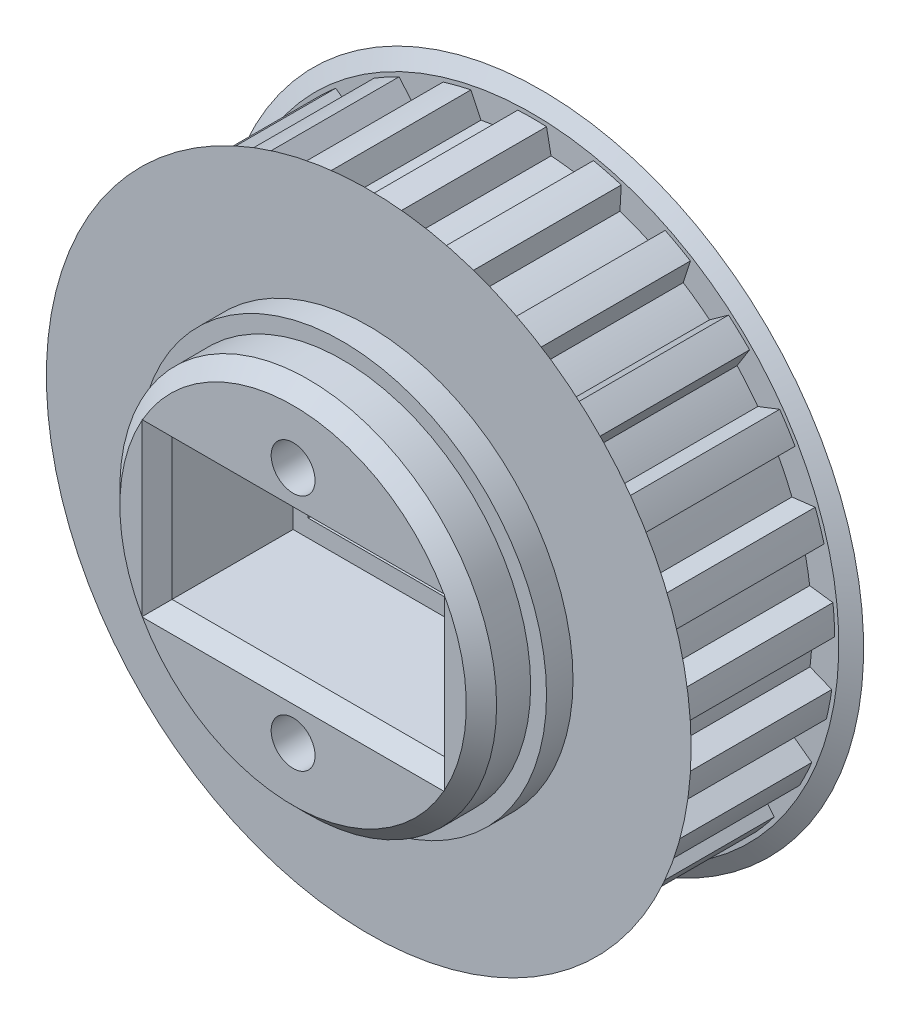
SolidWorks part; units mm, degrees
material "ABS"
ref_plane "Alzado" through (0, 0, 0) normal (0, 0, 1) x (1, 0, 0)
ref_plane "Planta" through (0, 0, 0) normal (0, 1, 0) x (1, 0, 0)
ref_plane "Vista lateral" through (0, 0, 0) normal (1, 0, 0) x (0, 0, -1)
sketch "Croquis1" plane through (0, 0, 0) normal (0, 0, 1) x (1, 0, 0)
  line L0 (0, 0) -> (0, 14.5885) construction
  line L1 (-0.95, 19.9774) -> (-1.25, 18.4577)
  line L2 (0.95, 19.9774) -> (1.25, 18.4577)
  line L3 (5.8883, 19.1135) -> (5.801, 17.567)
  line L4 (4.048, 19.5861) -> (3.3795, 18.1887)
  line L5 (10.4567, 17.0487) -> (9.9875, 15.5724)
  line L6 (8.7917, 17.964) -> (7.7967, 16.7768)
  line L7 (14.368, 13.9126) -> (13.5464, 12.5994)
  line L8 (12.983, 15.2132) -> (11.724, 14.3108)
  line L9 (17.3765, 9.9023) -> (16.2542, 8.8347)
  line L10 (16.3585, 11.5066) -> (14.9146, 10.9456)
  line L11 (19.2932, 5.2699) -> (17.9406, 4.5149)
  line L12 (18.7061, 7.0769) -> (17.1681, 6.8926)
  line L13 (19.9977, 0.3063) -> (18.4998, -0.0886)
  line L14 (19.8784, 2.2025) -> (18.3428, 2.4065)
  line L15 (19.4456, -4.6766) -> (17.8966, -4.6865)
  line L16 (19.8016, -2.8102) -> (18.365, -2.2308)
  line L17 (17.6716, -9.3656) -> (16.1688, -8.9899)
  line L18 (18.4806, -7.6464) -> (17.2333, -6.7279)
  line L19 (14.7873, -13.4661) -> (13.4251, -12.7285)
  line L20 (15.9984, -12.0021) -> (15.0187, -10.8023)
  line L21 (10.9739, -16.7205) -> (9.8379, -15.6673)
  line L22 (12.511, -15.6037) -> (11.8604, -14.1979)
  line L23 (6.4709, -18.9243) -> (5.6325, -17.6217)
  line L24 (8.2375, -18.2248) -> (7.957, -16.7014)
  line L25 (1.5613, -19.939) -> (1.0732, -18.4688)
  line L26 (3.4463, -19.7008) -> (3.5535, -18.1555)
  line L27 (-3.4463, -19.7008) -> (-3.5535, -18.1555)
  line L28 (-1.5613, -19.939) -> (-1.0732, -18.4688)
  line L29 (-8.2375, -18.2248) -> (-7.957, -16.7014)
  line L30 (-6.4709, -18.9243) -> (-5.6325, -17.6217)
  line L31 (-12.511, -15.6037) -> (-11.8604, -14.1979)
  line L32 (-10.9739, -16.7205) -> (-9.8379, -15.6673)
  line L33 (-15.9984, -12.0021) -> (-15.0187, -10.8023)
  line L34 (-14.7873, -13.4661) -> (-13.4251, -12.7285)
  line L35 (-18.4806, -7.6464) -> (-17.2333, -6.7279)
  line L36 (-17.6716, -9.3656) -> (-16.1688, -8.9899)
  line L37 (-19.8016, -2.8102) -> (-18.365, -2.2308)
  line L38 (-19.4456, -4.6766) -> (-17.8966, -4.6865)
  line L39 (-19.8784, 2.2025) -> (-18.3428, 2.4065)
  line L40 (-19.9977, 0.3063) -> (-18.4998, -0.0886)
  line L41 (-18.7061, 7.0769) -> (-17.1681, 6.8926)
  line L42 (-19.2932, 5.2699) -> (-17.9406, 4.5149)
  line L43 (-16.3585, 11.5066) -> (-14.9146, 10.9456)
  line L44 (-17.3765, 9.9023) -> (-16.2542, 8.8347)
  line L45 (-12.983, 15.2132) -> (-11.724, 14.3108)
  line L46 (-14.368, 13.9126) -> (-13.5464, 12.5994)
  line L47 (-8.7917, 17.964) -> (-7.7967, 16.7768)
  line L48 (-10.4567, 17.0487) -> (-9.9875, 15.5724)
  line L49 (-4.048, 19.5861) -> (-3.3795, 18.1887)
  line L50 (-5.8883, 19.1135) -> (-5.801, 17.567)
  arc A1 (3.3795, 18.1887) -> (1.25, 18.4577) centre (0, 0) ccw
  arc A9 (-4.048, 19.5861) -> (-5.8883, 19.1135) centre (0, 0) ccw
  arc A10 (-8.7917, 17.964) -> (-10.4567, 17.0487) centre (0, 0) ccw
  arc A11 (5.8883, 19.1135) -> (4.048, 19.5861) centre (0, 0) ccw
  arc A12 (0.95, 19.9774) -> (-0.95, 19.9774) centre (0, 0) ccw
  arc A16 (10.4567, 17.0487) -> (8.7917, 17.964) centre (0, 0) ccw
  arc A17 (14.368, 13.9126) -> (12.983, 15.2132) centre (0, 0) ccw
  arc A18 (17.3765, 9.9023) -> (16.3585, 11.5066) centre (0, 0) ccw
  arc A19 (19.2932, 5.2699) -> (18.7061, 7.0769) centre (0, 0) ccw
  arc A20 (19.9977, 0.3063) -> (19.8784, 2.2025) centre (0, 0) ccw
  arc A21 (19.4456, -4.6766) -> (19.8016, -2.8102) centre (0, 0) ccw
  arc A22 (17.6716, -9.3656) -> (18.4806, -7.6464) centre (0, 0) ccw
  arc A23 (14.7873, -13.4661) -> (15.9984, -12.0021) centre (0, 0) ccw
  arc A24 (10.9739, -16.7205) -> (12.511, -15.6037) centre (0, 0) ccw
  arc A25 (6.4709, -18.9243) -> (8.2375, -18.2248) centre (0, 0) ccw
  arc A26 (-12.511, -15.6037) -> (-10.9739, -16.7205) centre (0, 0) ccw
  arc A27 (-15.9984, -12.0021) -> (-14.7873, -13.4661) centre (0, 0) ccw
  arc A28 (-18.4806, -7.6464) -> (-17.6716, -9.3656) centre (0, 0) ccw
  arc A29 (-19.8784, 2.2025) -> (-19.9977, 0.3063) centre (0, 0) ccw
  arc A30 (-18.7061, 7.0769) -> (-19.2932, 5.2699) centre (0, 0) ccw
  arc A31 (-16.3585, 11.5066) -> (-17.3765, 9.9023) centre (0, 0) ccw
  arc A32 (-12.983, 15.2132) -> (-14.368, 13.9126) centre (0, 0) ccw
  arc A33 (-8.2375, -18.2248) -> (-6.4709, -18.9243) centre (0, 0) ccw
  arc A34 (-3.4463, -19.7008) -> (-1.5613, -19.939) centre (0, 0) ccw
  arc A35 (1.5613, -19.939) -> (3.4463, -19.7008) centre (0, 0) ccw
  arc A36 (7.7967, 16.7768) -> (5.801, 17.567) centre (0, 0) ccw
  arc A37 (11.724, 14.3108) -> (9.9875, 15.5724) centre (0, 0) ccw
  arc A39 (-1.25, 18.4577) -> (-3.3795, 18.1887) centre (0, 0) ccw
  arc A43 (14.9146, 10.9456) -> (13.5464, 12.5994) centre (0, 0) ccw
  arc A44 (17.1681, 6.8926) -> (16.2542, 8.8347) centre (0, 0) ccw
  arc A45 (18.3428, 2.4065) -> (17.9406, 4.5149) centre (0, 0) ccw
  arc A46 (18.365, -2.2308) -> (18.4998, -0.0886) centre (0, 0) ccw
  arc A47 (17.2333, -6.7279) -> (17.8966, -4.6865) centre (0, 0) ccw
  arc A48 (15.0187, -10.8023) -> (16.1688, -8.9899) centre (0, 0) ccw
  arc A49 (11.8604, -14.1979) -> (13.4251, -12.7285) centre (0, 0) ccw
  arc A50 (7.957, -16.7014) -> (9.8379, -15.6673) centre (0, 0) ccw
  arc A51 (3.5535, -18.1555) -> (5.6325, -17.6217) centre (0, 0) ccw
  arc A52 (-1.0732, -18.4688) -> (1.0732, -18.4688) centre (0, 0) ccw
  arc A53 (-5.6325, -17.6217) -> (-3.5535, -18.1555) centre (0, 0) ccw
  arc A54 (-9.8379, -15.6673) -> (-7.957, -16.7014) centre (0, 0) ccw
  arc A55 (-13.4251, -12.7285) -> (-11.8604, -14.1979) centre (0, 0) ccw
  arc A56 (-16.1688, -8.9899) -> (-15.0187, -10.8023) centre (0, 0) ccw
  arc A57 (-17.8966, -4.6865) -> (-17.2333, -6.7279) centre (0, 0) ccw
  arc A58 (-18.4998, -0.0886) -> (-18.365, -2.2308) centre (0, 0) ccw
  arc A59 (-17.9406, 4.5149) -> (-18.3428, 2.4065) centre (0, 0) ccw
  arc A60 (-16.2542, 8.8347) -> (-17.1681, 6.8926) centre (0, 0) ccw
  arc A61 (-13.5464, 12.5994) -> (-14.9146, 10.9456) centre (0, 0) ccw
  arc A62 (-9.9875, 15.5724) -> (-11.724, 14.3108) centre (0, 0) ccw
  arc A63 (-5.801, 17.567) -> (-7.7967, 16.7768) centre (0, 0) ccw
  arc A71 (-19.8016, -2.8102) -> (-19.4456, -4.6766) centre (0, 0) ccw
  circle A72 centre (0, 0) radius 1.5
  point P10 (-3.2613, 18.1887)
  point P151 (0, 0)
  dimension "D1" = 20
  dimension "D6" = 3
  dimension "D5" = 1.5
  dimension "D2" = 2.5
  dimension "D3" = 1.9
  dimension "D4" = 25
extrude "Saliente-Extruir1" add sketch "Croquis1" along normal blind 10.2
sketch "Croquis2" plane through (0, 0, 10.2) normal (0, 0, 1) x (1, 0, 0)
  circle A0 centre (0, 0) radius 22
  circle A1 centre (0, 0) radius 1.5
  circle A2 centre (0, 0) radius 1.5 construction
  dimension "D1" = 44
extrude "Saliente-Extruir2" add sketch "Croquis2" along normal blind 0.6
sketch "Croquis3" plane through (0, 0, 10.8) normal (0, 0, 1) x (1, 0, 0)
  circle A0 centre (0, 0) radius 1.5
  circle A1 centre (0, 0) radius 12.45
  circle A3 centre (0, 0) radius 1.5 construction
  dimension "D1" = 24.9
sketch "Croquis4" plane through (0, 0, 0) normal (0, 0, -1) x (-1, 0, 0)
  circle A0 centre (0, 0) radius 1.5
  circle A1 centre (0, 0) radius 12.45
  circle A2 centre (0, 0) radius 1.5 construction
  dimension "D1" = 24.9
extrude "Saliente-Extruir4" add sketch "Croquis4" along normal blind 4.25
sketch "Croquis6" plane through (0, 0, 0) normal (0, 0, -1) x (-1, 0, 0)
  circle A0 centre (0, 0) radius 22
  circle A1 centre (0, 0) radius 1.5
  circle A2 centre (0, 0) radius 1.5 construction
  dimension "D1" = 44
extrude "Saliente-Extruir6" add sketch "Croquis6" along normal blind 0.6
sketch "Croquis5" plane through (0, 0, -0.6) normal (0, 0, -1) x (-1, 0, 0)
  circle A0 centre (0, 0) radius 1.5
  circle A1 centre (0, 0) radius 13.5
  circle A2 centre (0, 0) radius 1.5 construction
  dimension "D1" = 27
extrude "Saliente-Extruir5" add sketch "Croquis5" along normal blind 1.75
chamfer "Chaflán2" distance 1 angle 60 2 edges at (-22, 0, 0) (22, 0, 10.2)
extrude "Saliente-Extruir7" add sketch "Croquis3" along normal blind 5
chamfer "Chaflán4" distance 1 angle 45 1 edges at (12.45, 0, 15.8)
sketch "Croquis7" plane through (0, 0, 10.8) normal (0, 0, 1) x (1, 0, 0)
  circle A0 centre (0, 0) radius 1.5
  circle A1 centre (0, 0) radius 13.5
  circle A2 centre (0, 0) radius 1.5 construction
  dimension "D1" = 27
extrude "Saliente-Extruir8" add sketch "Croquis7" along normal blind 1.75
sketch "Croquis8" plane through (0, 0, 0) normal (0, 0, 1) x (1, 0, 0)
  line L0 (0, 0) -> (6.706, 0) construction
  line L1 (-8, 3.5) -> (8, 3.5)
  line L2 (-8, 3.5) -> (-8, -3.5)
  line L3 (-8, -3.5) -> (8, -3.5)
  line L4 (8, 3.5) -> (8, -3.5)
  line L5 (-8, 3.5) -> (8, -3.5) construction
  line L6 (-8, -3.5) -> (8, 3.5) construction
  circle A0 centre (0, 7.8756) radius 1.45
  circle A1 centre (0, -7.8756) radius 1.45
  point P0 (0, 0)
  dimension "D1" = 2.9
  dimension "D2" = 7
  dimension "D3" = 16
extrude "Cortar-Extruir1" cut sketch "Croquis8" against normal through all both and the other way through all
sketch "Croquis10" plane through (0, 0, 15.8) normal (0, 0, 1) x (1, 0, 0)
  line L1 (9, 4.65) -> (-9, 4.65)
  line L2 (9, 4.65) -> (9, -4.65)
  line L3 (9, -4.65) -> (-9, -4.65)
  line L4 (-9, 4.65) -> (-9, -4.65)
  line L5 (9, 4.65) -> (-9, -4.65) construction
  line L6 (9, -4.65) -> (-9, 4.65) construction
  point P0 (0, 0)
  dimension "D1" = 9.3
  dimension "D2" = 18
extrude "Cortar-Extruir3" cut sketch "Croquis10" against normal blind 9
chamfer "Chaflán5" distance 1 angle 45 8 edges at (-8, 0, -4.25) (0, 3.5, -4.25) (8, 0, -4.25) (0, -3.5, -4.25) (9, 0, 15.8) (0, 4.65, 15.8) (-9, 0, 15.8) (0, -4.65, 15.8)
sketch "Sketch1" plane through (0, 0, -4.25) normal (0, 0, -1) x (-1, 0, 0)
  circle A0 centre (0, 0) radius 12.45
  circle A1 centre (0, 0) radius 12.45 construction
  circle A2 centre (0, 7.8756) radius 1.45
  circle A3 centre (0, -7.8756) radius 1.45
  circle A4 centre (0, 7.8756) radius 1.45 construction
extrude "Boss-Extrude1" add sketch "Sketch1" against normal blind 5
sketch "Sketch2" plane through (0, 0, -4.25) normal (0, 0, -1) x (-1, 0, 0)
  line L0 (0, 17.274) -> (0, -20.0751) construction
  line L1 (-7.5, 0) -> (7.5, 0) construction
  circle A0 centre (-7.5, 0) radius 1.45
  circle A1 centre (7.5, 0) radius 1.45
  dimension "D1" = 2.9
  dimension "D2" = 15
extrude "Cut-Extrude1" cut sketch "Sketch2" against normal through all
sketch "Sketch4" plane through (0, 0, 15.8) normal (0, 0, 1) x (1, 0, 0)
  line L0 (-8, -3.5) -> (8, -3.5) construction
  line L1 (4, 3.5) -> (-4, 3.5)
  line L2 (4, 3.5) -> (4, -3.5)
  line L3 (4, -3.5) -> (-4, -3.5)
  line L4 (-4, 3.5) -> (-4, -3.5)
  line L5 (4, 3.5) -> (-4, -3.5) construction
  line L6 (4, -3.5) -> (-4, 3.5) construction
  point P0 (0, 0)
  dimension "D1" = 8
extrude "Cut-Extrude2" cut sketch "Sketch4" against normal blind 21
chamfer "Chamfer3" distance 1 angle 45 4 edges at (-4, 0, -4.25) (0, 3.5, -4.25) (4, 0, -4.25) (0, -3.5, -4.25)
chamfer "Chamfer2" distance 0.75 angle 45 1 edges at (-12.45, 0, -4.25)
